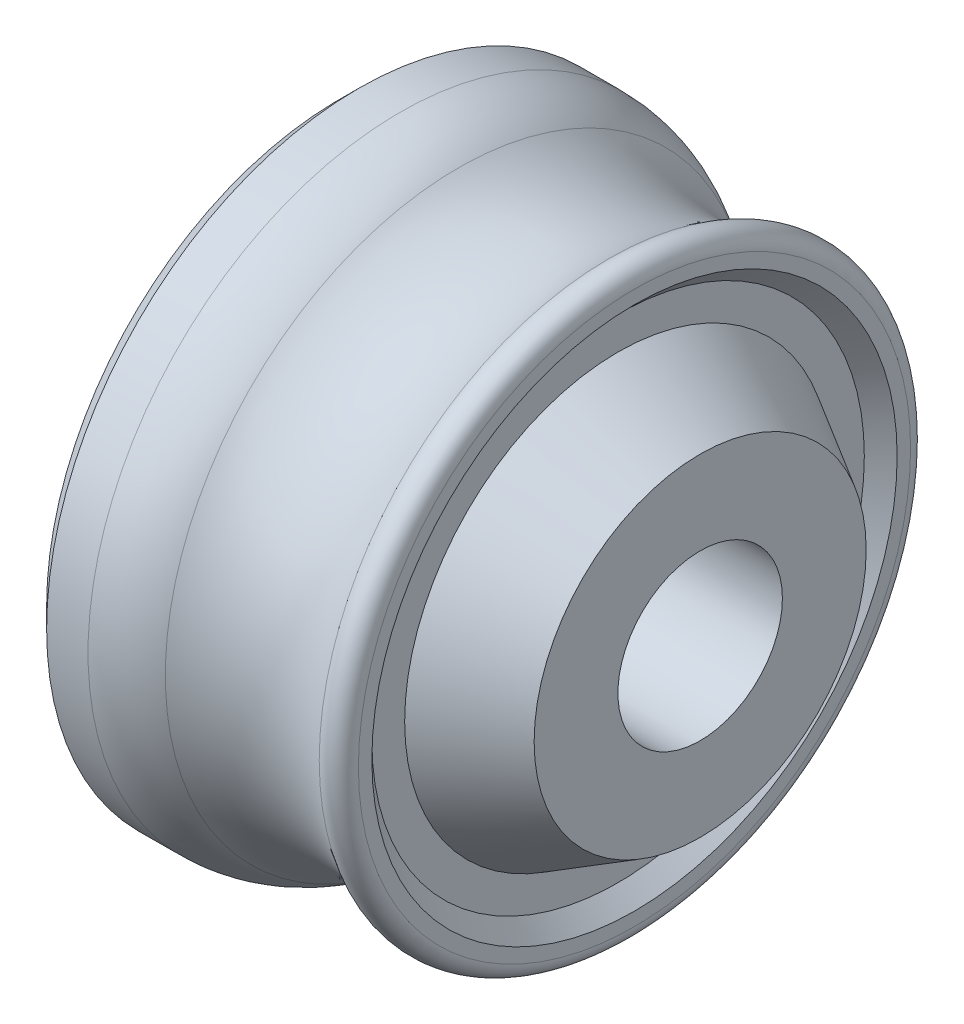
SolidWorks part; units mm, degrees
ref_plane "Front Plane" through (0, 0, 0) normal (0, 0, 1) x (1, 0, 0)
ref_plane "Top Plane" through (0, 0, 0) normal (0, 1, 0) x (1, 0, 0)
ref_plane "Right Plane" through (0, 0, 0) normal (1, 0, 0) x (0, 0, -1)
sketch "Sketch1" plane through (0, 0, 0) normal (0, 0, 1) x (1, 0, 0)
  line L0 (0, 0) -> (-14.7034, 0) construction
  line L1 (-3, -9.505) -> (-3, -2.505)
  line L2 (-3, -2.505) -> (3, -2.505)
  line L3 (3, -2.505) -> (3, -9.505)
  arc A1 (-3, -9.505) -> (3, -9.505) centre (0, -12.1508) cw
  point P5 (0, -2.505)
  dimension "D3" = 4
  dimension "D1" = 6
  dimension "D2" = 2.505
  dimension "D4" = 7
revolve "Revolve1" add sketch "Sketch1" angle 360 about L0
sketch "Sketch2" plane through (3, 0, 0) normal (1, 0, 0) x (0, 0, -1)
  circle A0 centre (0, 0) radius 7
  circle A1 centre (0, 0) radius 4.5
  dimension "D1" = 14
  dimension "D2" = 9
extrude "Cut-Extrude1" cut sketch "Sketch2" against normal blind 0.5
chamfer "Chamfer3" distance 1 angle 45 1 edges at (3, 0, -7)
sketch "Sketch3" plane through (3, 0, 0) normal (1, 0, 0) x (0, 0, -1)
  circle A0 centre (0, 0) radius 2.505 construction
  circle A1 centre (0, 0) radius 4.5
  circle A3 centre (0, 0) radius 2.505
  circle A8 centre (0, 0) radius 4.5
  dimension "D1" = 0
extrude "Boss-Extrude1" add sketch "Sketch3" along normal blind 2
chamfer "Chamfer4" distance 2 angle 60 1 edges at (2.5, 0, -4.5) first distance on face at (2.5, 0, -7.5)
sketch "Sketch4" plane through (-3, 0, 0) normal (-1, 0, 0) x (0, 0, 1)
  circle A0 centre (0, 0) radius 2.505 construction
  circle A1 centre (0, 0) radius 9.505
  circle A3 centre (0, 0) radius 2.505
  circle A6 centre (0, 0) radius 9.505
  dimension "D1" = 0
extrude "Boss-Extrude2" add sketch "Sketch4" along normal blind 3
fillet "Fillet1" radius 0.5 1 edges at (3, 0, -9.505)
fillet "Fillet2" radius 3 1 edges at (-3, 0, 9.505)
chamfer "Chamfer5" distance 0.6 angle 45 2 edges at (-6, 0, 2.505) (-6, 0, 9.505)
